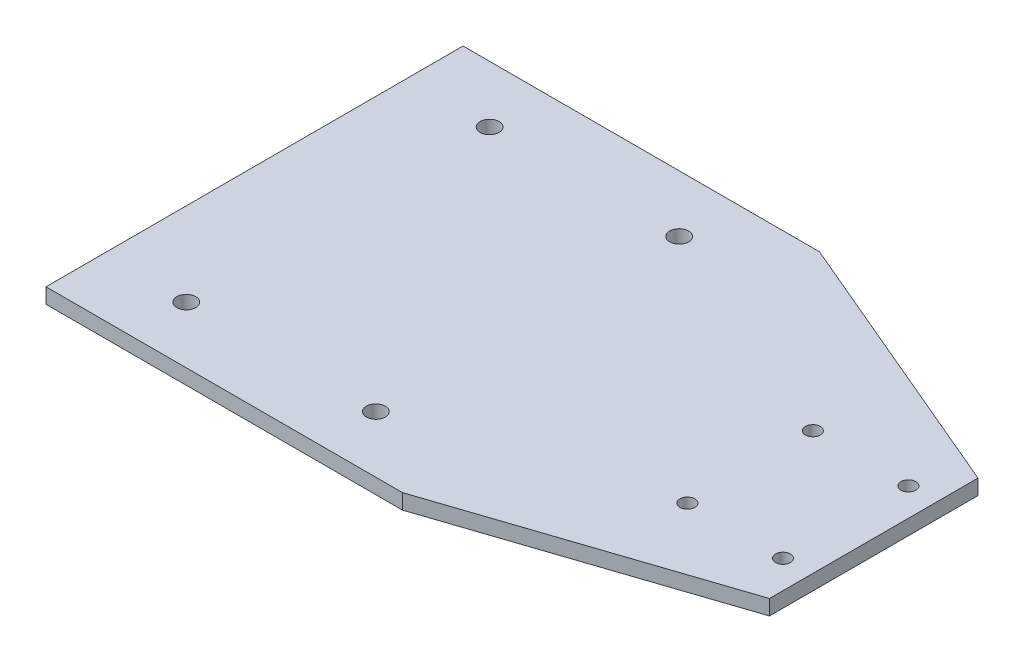
SolidWorks part; units mm, degrees
ref_plane "Front Plane" through (0, 0, 0) normal (0, 0, 1) x (1, 0, 0)
ref_plane "Top Plane" through (0, 0, 0) normal (0, 1, 0) x (1, 0, 0)
ref_plane "Right Plane" through (0, 0, 0) normal (1, 0, 0) x (0, 0, -1)
sketch "Sketch1" plane through (0, 0, 0) normal (0, 1, 0) x (1, 0, 0)
  line L0 (75.945, 15.3764) -> (29.845, 34.925)
  line L1 (-15.875, -25.4) -> (15.875, -25.4) construction
  line L2 (-15.875, -25.4) -> (-15.875, 25.4) construction
  line L3 (-15.875, 25.4) -> (15.875, 25.4) construction
  line L4 (15.875, -25.4) -> (15.875, 25.4) construction
  line L5 (-15.875, -25.4) -> (15.875, 25.4) construction
  line L6 (-15.875, 25.4) -> (15.875, -25.4) construction
  line L7 (29.845, -34.925) -> (-29.845, -34.925)
  line L8 (29.845, -34.925) -> (29.845, 34.925) construction
  line L9 (29.845, 34.925) -> (-29.845, 34.925)
  line L10 (-29.845, -34.925) -> (-29.845, 34.925)
  line L11 (29.845, -34.925) -> (-29.845, 34.925) construction
  line L12 (29.845, 34.925) -> (-29.845, -34.925) construction
  line L13 (55.245, -12.5861) -> (71.245, -12.5861) construction
  line L14 (55.245, -12.5861) -> (55.245, 8.4139) construction
  line L15 (55.245, 8.4139) -> (71.245, 8.4139) construction
  line L16 (71.245, -12.5861) -> (71.245, 8.4139) construction
  line L17 (55.245, -12.5861) -> (71.245, 8.4139) construction
  line L18 (55.245, 8.4139) -> (71.245, -12.5861) construction
  line L19 (50.545, 15.3764) -> (75.945, 15.3764) construction
  line L20 (50.545, 15.3764) -> (50.545, -19.5486) construction
  line L21 (50.545, -19.5486) -> (75.945, -19.5486) construction
  line L22 (75.945, 15.3764) -> (75.945, -19.5486)
  line L23 (50.545, 15.3764) -> (75.945, -19.5486) construction
  line L24 (50.545, -19.5486) -> (75.945, 15.3764) construction
  line L25 (75.945, -19.5486) -> (29.845, -34.925)
  circle A0 centre (-15.875, 25.4) radius 1.5875
  circle A1 centre (15.875, 25.4) radius 1.5875
  circle A2 centre (15.875, -25.4) radius 1.5875
  circle A3 centre (-15.875, -25.4) radius 1.5875
  circle A4 centre (71.245, 8.4139) radius 1.25
  circle A5 centre (71.245, -12.5861) radius 1.25
  circle A6 centre (55.245, -12.5861) radius 1.25
  circle A8 centre (55.245, 8.4139) radius 1.25
  point P0 (0, 0)
  point P7 (0, 0)
  point P15 (63.245, -2.0861)
  point P21 (0, 0)
  point P23 (63.245, -2.0861)
  dimension "D3" = 3.175
  dimension "D8" = 2.5
  dimension "D1" = 50.8
  dimension "D2" = 31.75
  dimension "D4" = 69.85
  dimension "D5" = 13.97
  dimension "D6" = 21
  dimension "D7" = 16
  dimension "D9" = 25.4
  dimension "D10" = 34.925
  dimension "D11" = 25.4
extrude "Boss-Extrude1" add sketch "Sketch1" along normal blind 2.54
